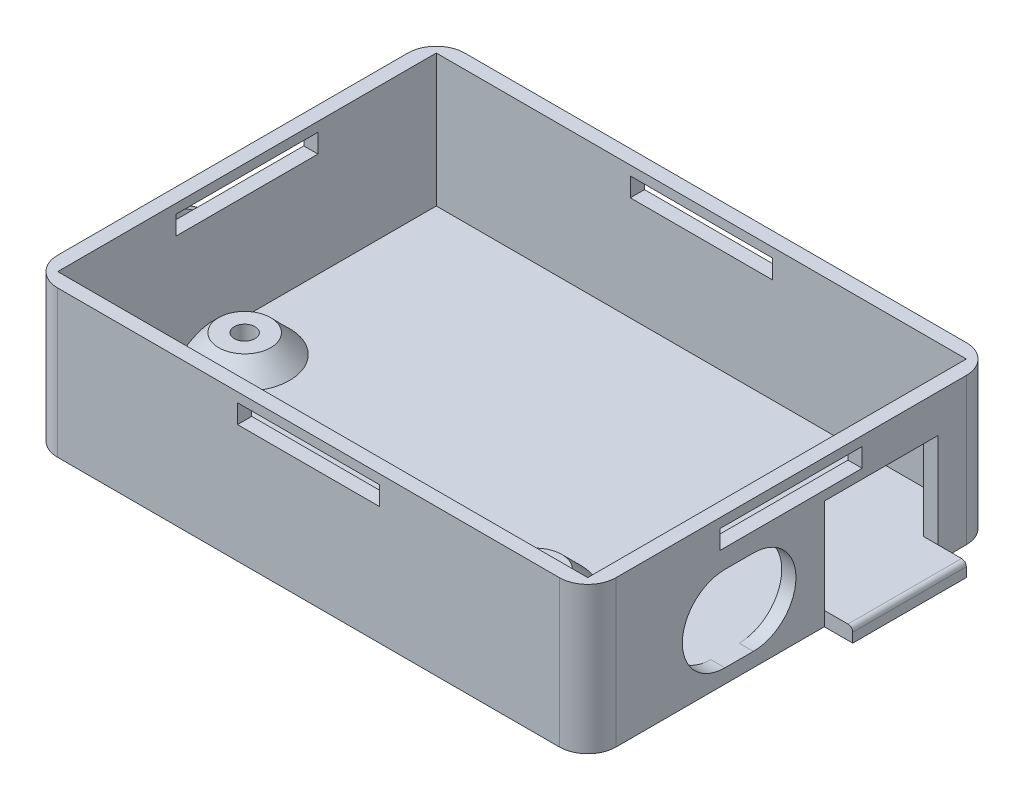
SolidWorks part; units mm, degrees
ref_plane "Front" through (0, 0, 0) normal (0, 0, 1) x (1, 0, 0)
ref_plane "Top" through (0, 0, 0) normal (0, 1, 0) x (1, 0, 0)
ref_plane "Right" through (0, 0, 0) normal (1, 0, 0) x (0, 0, -1)
sketch "Sketch1" plane through (0, 0, 0) normal (0, 1, 0) x (1, 0, 0)
  line L1 (-29.5, -21.5) -> (29.5, -21.5)
  line L2 (-29.5, -21.5) -> (-29.5, 21.5)
  line L3 (-29.5, 21.5) -> (29.5, 21.5)
  line L4 (29.5, -21.5) -> (29.5, 21.5)
  line L5 (-29.5, -21.5) -> (29.5, 21.5) construction
  line L6 (-29.5, 21.5) -> (29.5, -21.5) construction
  line L7 (-27, -19) -> (27, -19) construction
  line L8 (-27, -19) -> (-27, 19) construction
  line L9 (-27, 19) -> (27, 19) construction
  line L10 (27, -19) -> (27, 19) construction
  line L11 (-27, -19) -> (27, 19) construction
  line L12 (-27, 19) -> (27, -19) construction
  point P0 (0, 0)
  point P6 (0, 0)
  dimension "D1" = 2.5
  dimension "D2" = 2.5
  dimension "D3" = 54
  dimension "D4" = 38
extrude "Boss-Extrude1" add sketch "Sketch1" along normal blind 1.5
sketch "Sketch2" plane through (0, 1.5, 0) normal (0, 1, 0) x (1, 0, 0)
  line L0 (29.5, 21.5) -> (-29.5, 21.5) construction
  line L1 (-28, -20) -> (28, -20)
  line L2 (-28, -20) -> (-28, 20)
  line L3 (-28, 20) -> (28, 20)
  line L4 (28, -20) -> (28, 20)
  line L5 (-28, -20) -> (28, 20) construction
  line L6 (-28, 20) -> (28, -20) construction
  line L7 (-29.5, 21.5) -> (-29.5, -21.5) construction
  point P0 (0, 0)
  line M5 (29.5, -21.5) -> (29.5, 21.5)
  line M6 (29.5, 21.5) -> (-29.5, 21.5)
  line M7 (-29.5, 21.5) -> (-29.5, -21.5)
  line M8 (-29.5, -21.5) -> (29.5, -21.5)
  dimension "D1" = 1.5
  dimension "D2" = 1.5
extrude "Boss-Extrude2" add sketch "Sketch2" along normal blind 14 contours L4 L1 L2 L3 M8 M5 M6 M7 region at (0, 1.5, 20.7699)
sketch "Sketch3" plane through (0, 1.5, 0) normal (0, 1, 0) x (1, 0, 0)
  circle A0 centre (-24.5359, -3.71) radius 2.75
  circle A1 centre (12.5, -10) radius 2.75
  circle A2 centre (-24.5359, -3.71) radius 1.6 construction
  dimension "D1" = 5.5
extrude "Boss-Extrude3" add sketch "Sketch3" along normal blind 2
sketch "Sketch5" plane through (29.5, 0, 0) normal (1, 0, 0) x (0, 0, -1)
  line L0 (-7, 6) -> (-4, 6) construction
  line L1 (-7, 10.5) -> (-4, 10.5)
  line L2 (-7, 1.5) -> (-4, 1.5)
  line L3 (-20, 1.5) -> (20, 1.5) construction
  arc A0 (-7, 10.5) -> (-7, 1.5) centre (-7, 6) ccw
  arc A1 (-4, 1.5) -> (-4, 10.5) centre (-4, 6) ccw
  point P2 (-5.5, 6)
  point P7 (-11.5, 6)
  point P8 (0.5, 6)
  dimension "D1" = 9
  dimension "D2" = 12
  dimension "D3" = 8.5
extrude "Cut-Extrude1" cut sketch "Sketch5" against normal up to next
fillet "Fillet4" radius 3 4 edges at (-29.5, 7.75, -21.5) (29.5, 7.75, 21.5) (-29.5, 7.75, 21.5) (29.5, 7.75, -21.5)
sketch "Sketch10" plane through (0, 0, 0) normal (0, -1, 0) x (1, 0, 0)
  line L0 (-24.5359, 6.0194) -> (-26.5359, 4.8647)
  line L1 (-26.5359, 4.8647) -> (-26.5359, 2.5553)
  line L2 (-26.5359, 2.5553) -> (-24.5359, 1.4006)
  line L3 (-24.5359, 1.4006) -> (-22.5359, 2.5553)
  line L4 (-22.5359, 2.5553) -> (-22.5359, 4.8647)
  line L5 (-22.5359, 4.8647) -> (-24.5359, 6.0194)
  line L6 (11.3453, 12) -> (13.6547, 12)
  line L7 (13.6547, 12) -> (14.8094, 10)
  line L8 (14.8094, 10) -> (13.6547, 8)
  line L9 (13.6547, 8) -> (11.3453, 8)
  line L10 (11.3453, 8) -> (10.1906, 10)
  line L11 (10.1906, 10) -> (11.3453, 12)
  circle A0 centre (-24.5359, 3.71) radius 2.3094 construction
  circle A1 centre (12.5, 10) radius 2.3094 construction
  circle A3 centre (-24.5359, 3.71) radius 2.75 construction
  circle A4 centre (12.5, 10) radius 2.75 construction
  dimension "D1" = 4
extrude "Cut-Extrude4" cut sketch "Sketch10" against normal blind 1.7
chamfer "Chamfer1" distance 2 angle 45 2 edges at (12.5, 1.5, 7.25) (-24.5359, 1.5, 0.96)
sketch "Sketch11" plane through (0, 3.5, 0) normal (0, 1, 0) x (1, 0, 0)
  circle A0 centre (-24.5359, -3.71) radius 1.1
  circle A1 centre (12.5, -10) radius 1.1
  dimension "D1" = 2.2
extrude "Cut-Extrude5" cut sketch "Sketch11" against normal through all
sketch "Sketch12" plane through (0, 0, -21.5) normal (0, 0, -1) x (-1, 0, 0)
  line L0 (-26.5, 15.5) -> (26.5, 15.5) construction
  line L1 (-7.5, 12.5) -> (7.5, 12.5)
  line L2 (-7.5, 12.5) -> (-7.5, 14.5)
  line L3 (-7.5, 14.5) -> (7.5, 14.5)
  line L4 (7.5, 12.5) -> (7.5, 14.5)
  line L5 (-7.5, 12.5) -> (7.5, 14.5) construction
  line L6 (-7.5, 14.5) -> (7.5, 12.5) construction
  point P0 (0, 13.5)
  dimension "D1" = 1
  dimension "D2" = 2
  dimension "D3" = 15
extrude "Cut-Extrude6" cut sketch "Sketch12" against normal through all
mirror "Mirror1" [suppressed] about plane through (0, 0, 0) normal (0, 0, 1)
sketch "Sketch13" plane through (-29.5, 0, 0) normal (-1, 0, 0) x (0, 0, 1)
  line L0 (-18.5, 15.5) -> (18.5, 15.5) construction
  line L1 (-7.5, 12.5) -> (7.5, 12.5)
  line L2 (-7.5, 12.5) -> (-7.5, 14.5)
  line L3 (-7.5, 14.5) -> (7.5, 14.5)
  line L4 (7.5, 12.5) -> (7.5, 14.5)
  line L5 (-7.5, 12.5) -> (7.5, 14.5) construction
  line L6 (-7.5, 14.5) -> (7.5, 12.5) construction
  point P0 (0, 13.5)
  dimension "D1" = 2
  dimension "D2" = 1
  dimension "D3" = 15
extrude "Cut-Extrude7" cut sketch "Sketch13" against normal through all
mirror "Mirror2" [suppressed] about plane through (0, 0, 0) normal (1, 0, 0)
sketch "Sketch14" plane through (0, 0, -21.5) normal (0, 0, -1) x (-1, 0, 0)
  line L0 (-26.5, 15.5) -> (-26.5, 0) construction
  line L1 (-26.5, 13.5) -> (-16.5, 13.5)
  line L2 (-26.5, 13.5) -> (-26.5, 3.5)
  line L3 (-26.5, 3.5) -> (-16.5, 3.5)
  line L4 (-16.5, 13.5) -> (-16.5, 3.5)
  line L7 (28, 1.5) -> (-28, 1.5) construction
  point P6 (-16.5, 13.0598)
  dimension "D1" = 2
  dimension "D2" = 10
  dimension "D3" = 10
extrude "Cut-Extrude8" [suppressed] cut sketch "Sketch14" against normal blind 2
sketch "Sketch7" plane through (0, 0, 0) normal (0, -1, 0) x (1, 0, 0)
  line L0 (-29.5, -18.5) -> (-29.5, 18.5) construction
  line L1 (29.5, 18.5) -> (29.5, -18.5) construction
  line L2 (-29.5, -6) -> (-40.5, -6)
  line L3 (-29.5, -6) -> (-29.5, 6)
  line L4 (-29.5, 6) -> (-40.5, 6)
  line L5 (-40.5, -6) -> (-40.5, 6)
  line L7 (29.5, -18.5) -> (40.5, -18.5)
  line L8 (29.5, -18.5) -> (29.5, -6.5)
  line L9 (29.5, -6.5) -> (40.5, -6.5)
  line L10 (40.5, -18.5) -> (40.5, -6.5)
  point P6 (-40.5, 0)
  point P7 (-29.5, 0)
  point P8 (-29.5, 0)
  point P9 (40.5, -12.5)
  point P16 (-35, -6)
  point P17 (35, -18.5)
  line M11 (-29.5, 18.5) -> (-29.5, -18.5)
  dimension "D1" = 12.5
  dimension "D2" = 70
  dimension "D3" = 12
extrude "Boss-Extrude4" add sketch "Sketch7" against normal blind 5 contours L5 L2 L4 M11 region at (-35, 0, 0)
sketch "Sketch8" plane through (0, 5, 0) normal (0, 1, 0) x (1, 0, 0)
  line L6 (-29.5, 6) -> (-40.5, 6) construction
  line L7 (-40.5, 6) -> (-40.5, -6) construction
  circle A0 centre (35, 12.5) radius 2
  circle A1 centre (-35, 0) radius 2
  point P4 (0, 0)
  point P5 (0, 0)
  point P9 (-35, 6)
  point P14 (0, 0)
  point P18 (-40.5, 0)
  dimension "D1" = 4
extrude "Cut-Extrude2" cut sketch "Sketch8" against normal through all
fillet "Fillet1" radius 3.5 4 edges at (-40.5, 2.5, -6) (-29.5, 2.5, -6) (-40.5, 2.5, 6) (-29.5, 2.5, 6)
fillet "Fillet2" radius 4 1 edges at (-29.5, 5, 0)
fillet "Fillet3" radius 3.5 9 edges at (-31.1871, 5.7365, -6.5061) (-33.2495, 5.0079, -6) (-35.25, 5, -6) (-39.4749, 5, -4.9749) (-40.5, 5, 0) (-39.4749, 5, 4.9749) (-35.25, 5, 6) (-33.2495, 5.0079, 6) (-31.1871, 5.7365, 6.5061)
sketch "Sketch9" plane through (0, 5, 0) normal (0, 1, 0) x (1, 0, 0)
  circle A0 centre (-35, 0) radius 4
  circle A1 centre (35, 12.5) radius 4
  dimension "D1" = 8
extrude "Cut-Extrude3" cut sketch "Sketch9" against normal blind 2 and the other way through all
sketch "Sketch15" plane through (29.5, 0, 0) normal (1, 0, 0) x (0, 0, -1)
  line L0 (-18.5, 0) -> (18.5, 0) construction
  line L1 (15.5, 0) -> (3.5, 0)
  line L2 (15.5, 0) -> (15.5, 1.5)
  line L3 (15.5, 1.5) -> (3.5, 1.5)
  line L4 (3.5, 0) -> (3.5, 1.5)
  line L5 (18.5, 0) -> (18.5, 15.5) construction
  point P5 (16.9518, 0)
  dimension "D1" = 12
  dimension "D2" = 1.5
  dimension "D3" = 3
extrude "Boss-Extrude6" add sketch "Sketch15" along normal blind 3
fillet "Fillet5" radius 0.5 1 edges at (32.5, 1.5, -9.5)
sketch "Sketch16" plane through (29.5, 0, 0) normal (1, 0, 0) x (0, 0, -1)
  line L1 (15.5, 1.5) -> (3.5, 1.5)
  line L2 (15.5, 1.5) -> (15.5, 11.5)
  line L3 (15.5, 11.5) -> (3.5, 11.5)
  line L4 (3.5, 1.5) -> (3.5, 11.5)
  point P5 (8.5, 1.5)
  point P7 (18.5, 7.7365)
  point P8 (16.5, 1.5)
  point P10 (18.5, 1.5)
  dimension "D1" = 10
extrude "Cut-Extrude9" cut sketch "Sketch16" against normal up to next
